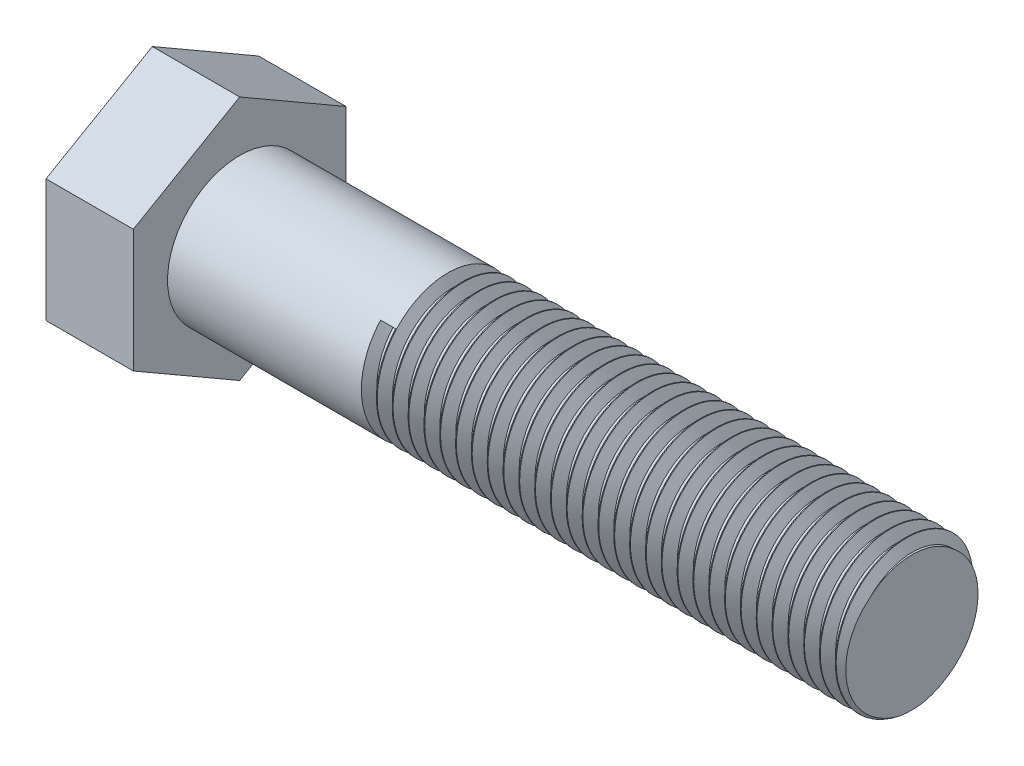
SolidWorks part; units mm, degrees
material "Chrome Stainless Steel"
ref_plane "Front Plane" through (0, 0, 0) normal (0, 0, 1) x (1, 0, 0)
ref_plane "Top Plane" through (0, 0, 0) normal (0, 1, 0) x (1, 0, 0)
ref_plane "Right Plane" through (0, 0, 0) normal (1, 0, 0) x (0, 0, -1)
sketch "Sketch1" plane through (0, 0, 0) normal (1, 0, 0) x (0, 0, -1)
  line L1 (0, -8.2122) -> (7.112, -4.1061)
  line L2 (7.112, -4.1061) -> (7.112, 4.1061)
  line L3 (7.112, 4.1061) -> (0, 8.2122)
  line L4 (0, 8.2122) -> (-7.112, 4.1061)
  line L5 (-7.112, 4.1061) -> (-7.112, -4.1061)
  line L6 (-7.112, -4.1061) -> (0, -8.2122)
  circle A0 centre (0, 0) radius 7.112 construction
  dimension "D1" = 14.224
extrude "Boss-Extrude1" add sketch "Sketch1" against normal blind 5.842
sketch "Sketch2" plane through (0, 0, 0) normal (1, 0, 0) x (0, 0, -1)
  circle A0 centre (0, 0) radius 4.826
  dimension "D1" = 9.652
extrude "Boss-Extrude2" add sketch "Sketch2" along normal blind 44.958
ref_plane "Plane1" through (44.958, 0, 0) normal (1, 0, 0) x (0, 0, -1)
sketch "Sketch6" plane through (44.958, 0, 0) normal (1, 0, 0) x (0, 0, -1)
  circle A0 centre (0, 0) radius 4.826
  dimension "D1" = 9.652
curve "Helix/Spiral1" pitch 1.0583 height 31.75 radius 4.826 centre (44.958, 0, 0) axis (-1, 0, 0) start towards (0, 0.7071, 0.7071)
sketch "Sketch7" plane through (0, 0, 0) normal (0, 0, 1) x (1, 0, 0)
  line L0 (44.958, 4.7545) -> (44.958, 5.1628) construction
  line L1 (44.958, -4.826) -> (44.958, 4.826) construction
  line L2 (44.4556, 4.826) -> (45.4604, 4.826)
  line L3 (45.4604, 4.826) -> (45.085, 4.1758)
  line L4 (45.085, 4.1758) -> (44.831, 4.1758)
  line L5 (44.958, 4.1758) -> (45.9904, 4.1758) construction
  line L7 (44.4556, 4.826) -> (44.831, 4.1758)
  spline S0 degree 3 poles (44.958, 3.4125) (44.9361, 3.8563) (44.8918, 4.576) (44.8257, 4.9513) (44.7596, 4.5748) (44.6934, 3.5013) (44.6273, 1.8949) (44.5611, 0) (44.495, -1.8949) (44.4288, -3.5013) (44.3627, -4.5747) (44.2965, -4.9516) (44.2304, -4.5747) (44.1643, -3.5013) (44.0761, -1.3594) (43.9879, 1.3594) (43.8997, 3.5013) (43.8335, 4.5747) (43.7674, 4.9516) (43.7012, 4.5747) (43.6351, 3.5013) (43.5469, 1.3594) (43.4587, -1.3594) (43.3705, -3.5013) (43.3044, -4.5747) (43.2382, -4.9516) (43.1721, -4.5747) (43.1059, -3.5013) (43.0177, -1.3594) (42.9295, 1.3594) (42.8413, 3.5013) (42.7752, 4.5747) (42.709, 4.9516) (42.6429, 4.5747) (42.5767, 3.5013) (42.4886, 1.3594) (42.4004, -1.3594) (42.3122, -3.5013) (42.246, -4.5747) (42.1799, -4.9516) (42.1137, -4.5747) (42.0476, -3.5013) (41.9594, -1.3594) (41.8712, 1.3594) (41.783, 3.5013) (41.7169, 4.5747) (41.6507, 4.9516) (41.5846, 4.5747) (41.5184, 3.5013) (41.4302, 1.3594) (41.342, -1.3594) (41.2538, -3.5013) (41.1877, -4.5747) (41.1215, -4.9516) (41.0554, -4.5747) (40.9893, -3.5013) (40.9011, -1.3594) (40.8129, 1.3594) (40.7247, 3.5013) (40.6585, 4.5747) (40.5924, 4.9516) (40.5262, 4.5747) (40.4601, 3.5013) (40.3719, 1.3594) (40.2837, -1.3594) (40.1955, -3.5013) (40.1294, -4.5747) (40.0632, -4.9516) (39.9971, -4.5747) (39.9309, -3.5013) (39.8427, -1.3594) (39.7545, 1.3594) (39.6663, 3.5013) (39.6002, 4.5747) (39.534, 4.9516) (39.4679, 4.5747) (39.4017, 3.5013) (39.3136, 1.3594) (39.2254, -1.3594) (39.1372, -3.5013) (39.071, -4.5747) (39.0049, -4.9516) (38.9387, -4.5747) (38.8726, -3.5013) (38.7844, -1.3594) (38.6962, 1.3594) (38.608, 3.5013) (38.5419, 4.5747) (38.4757, 4.9516) (38.4096, 4.5747) (38.3434, 3.5013) (38.2552, 1.3594) (38.167, -1.3594) (38.0788, -3.5013) (38.0127, -4.5747) (37.9465, -4.9516) (37.8804, -4.5747) (37.8143, -3.5013) (37.7261, -1.3594) (37.6379, 1.3594) (37.5497, 3.5013) (37.4835, 4.5747) (37.4174, 4.9516) (37.3512, 4.5747) (37.2851, 3.5013) (37.1969, 1.3594) (37.1087, -1.3594) (37.0205, -3.5013) (36.9544, -4.5747) (36.8882, -4.9516) (36.8221, -4.5747) (36.7559, -3.5013) (36.6677, -1.3594) (36.5795, 1.3594) (36.4913, 3.5013) (36.4252, 4.5747) (36.359, 4.9516) (36.2929, 4.5747) (36.2268, 3.5013) (36.1386, 1.3594) (36.0504, -1.3594) (35.9622, -3.5013) (35.896, -4.5747) (35.8299, -4.9516) (35.7637, -4.5747) (35.6976, -3.5013) (35.6094, -1.3594) (35.5212, 1.3594) (35.433, 3.5013) (35.3669, 4.5747) (35.3007, 4.9516) (35.2346, 4.5747) (35.1684, 3.5013) (35.0802, 1.3594) (34.992, -1.3594) (34.9038, -3.5013) (34.8377, -4.5747) (34.7715, -4.9516) (34.7054, -4.5747) (34.6393, -3.5013) (34.5511, -1.3594) (34.4629, 1.3594) (34.3747, 3.5013) (34.3085, 4.5747) (34.2424, 4.9516) (34.1762, 4.5747) (34.1101, 3.5013) (34.0219, 1.3594) (33.9337, -1.3594) (33.8455, -3.5013) (33.7794, -4.5747) (33.7132, -4.9516) (33.6471, -4.5747) (33.5809, -3.5013) (33.4927, -1.3594) (33.4045, 1.3594) (33.3163, 3.5013) (33.2502, 4.5747) (33.184, 4.9516) (33.1179, 4.5747) (33.0518, 3.5013) (32.9636, 1.3594) (32.8754, -1.3594) (32.7872, -3.5013) (32.721, -4.5747) (32.6549, -4.9516) (32.5887, -4.5747) (32.5226, -3.5013) (32.4344, -1.3594) (32.3462, 1.3594) (32.258, 3.5013) (32.1919, 4.5747) (32.1257, 4.9516) (32.0596, 4.5747) (31.9934, 3.5013) (31.9052, 1.3594) (31.817, -1.3594) (31.7288, -3.5013) (31.6627, -4.5747) (31.5965, -4.9516) (31.5304, -4.5747) (31.4643, -3.5013) (31.3761, -1.3594) (31.2879, 1.3594) (31.1997, 3.5013) (31.1335, 4.5747) (31.0674, 4.9516) (31.0012, 4.5747) (30.9351, 3.5013) (30.8469, 1.3594) (30.7587, -1.3594) (30.6705, -3.5013) (30.6044, -4.5747) (30.5382, -4.9516) (30.4721, -4.5747) (30.4059, -3.5013) (30.3177, -1.3594) (30.2295, 1.3594) (30.1413, 3.5013) (30.0752, 4.5747) (30.009, 4.9516) (29.9429, 4.5747) (29.8768, 3.5013) (29.7886, 1.3594) (29.7004, -1.3594) (29.6122, -3.5013) (29.546, -4.5747) (29.4799, -4.9516) (29.4137, -4.5747) (29.3476, -3.5013) (29.2594, -1.3594) (29.1712, 1.3594) (29.083, 3.5013) (29.0169, 4.5747) (28.9507, 4.9516) (28.8846, 4.5747) (28.8184, 3.5013) (28.7302, 1.3594) (28.642, -1.3594) (28.5538, -3.5013) (28.4877, -4.5747) (28.4215, -4.9516) (28.3554, -4.5747) (28.2893, -3.5013) (28.2011, -1.3594) (28.1129, 1.3594) (28.0247, 3.5013) (27.9585, 4.5747) (27.8924, 4.9516) (27.8262, 4.5747) (27.7601, 3.5013) (27.6719, 1.3594) (27.5837, -1.3594) (27.4955, -3.5013) (27.4294, -4.5747) (27.3632, -4.9516) (27.2971, -4.5747) (27.2309, -3.5013) (27.1427, -1.3594) (27.0545, 1.3594) (26.9663, 3.5013) (26.9002, 4.5747) (26.834, 4.9516) (26.7679, 4.5747) (26.7018, 3.5013) (26.6136, 1.3594) (26.5254, -1.3594) (26.4372, -3.5013) (26.371, -4.5747) (26.3049, -4.9516) (26.2387, -4.5747) (26.1726, -3.5013) (26.0844, -1.3594) (25.9962, 1.3594) (25.908, 3.5013) (25.8419, 4.5747) (25.7757, 4.9516) (25.7096, 4.5747) (25.6434, 3.5013) (25.5552, 1.3594) (25.467, -1.3594) (25.3788, -3.5013) (25.3127, -4.5747) (25.2465, -4.9516) (25.1804, -4.5747) (25.1143, -3.5013) (25.0261, -1.3594) (24.9379, 1.3594) (24.8497, 3.5013) (24.7835, 4.5747) (24.7174, 4.9516) (24.6512, 4.5747) (24.5851, 3.5013) (24.4969, 1.3594) (24.4087, -1.3594) (24.3205, -3.5013) (24.2544, -4.5747) (24.1882, -4.9516) (24.1221, -4.5747) (24.0559, -3.5013) (23.9677, -1.3594) (23.8795, 1.3594) (23.7913, 3.5013) (23.7252, 4.5747) (23.659, 4.9516) (23.5929, 4.5747) (23.5268, 3.5013) (23.4386, 1.3594) (23.3504, -1.3594) (23.2622, -3.5013) (23.196, -4.5747) (23.1299, -4.9516) (23.0637, -4.5747) (22.9976, -3.5013) (22.9094, -1.3594) (22.8212, 1.3594) (22.733, 3.5013) (22.6669, 4.5747) (22.6007, 4.9516) (22.5346, 4.5747) (22.4684, 3.5013) (22.3802, 1.3594) (22.292, -1.3594) (22.2038, -3.5013) (22.1377, -4.5747) (22.0715, -4.9516) (22.0054, -4.5747) (21.9393, -3.5013) (21.8511, -1.3594) (21.7629, 1.3594) (21.6747, 3.5013) (21.6085, 4.5747) (21.5424, 4.9516) (21.4762, 4.5747) (21.4101, 3.5013) (21.3219, 1.3594) (21.2337, -1.3594) (21.1455, -3.5013) (21.0794, -4.5747) (21.0132, -4.9516) (20.9471, -4.5747) (20.8809, -3.5013) (20.7927, -1.3594) (20.7045, 1.3594) (20.6163, 3.5013) (20.5502, 4.5747) (20.484, 4.9516) (20.4179, 4.5747) (20.3518, 3.5013) (20.2636, 1.3594) (20.1754, -1.3594) (20.0872, -3.5013) (20.021, -4.5747) (19.9549, -4.9516) (19.8887, -4.5747) (19.8226, -3.5013) (19.7344, -1.3594) (19.6462, 1.3594) (19.558, 3.5013) (19.4919, 4.5747) (19.4257, 4.9516) (19.3596, 4.5747) (19.2934, 3.5013) (19.2052, 1.3594) (19.117, -1.3594) (19.0288, -3.5013) (18.9627, -4.5747) (18.8965, -4.9516) (18.8304, -4.5747) (18.7643, -3.5013) (18.6761, -1.3594) (18.5879, 1.3594) (18.4997, 3.5013) (18.4335, 4.5747) (18.3674, 4.9516) (18.3012, 4.5747) (18.2351, 3.5013) (18.1469, 1.3594) (18.0587, -1.3594) (17.9705, -3.5013) (17.9044, -4.5747) (17.8382, -4.9516) (17.7721, -4.5747) (17.7059, -3.5013) (17.6177, -1.3594) (17.5295, 1.3594) (17.4413, 3.5013) (17.3752, 4.5747) (17.309, 4.9516) (17.2429, 4.5747) (17.1768, 3.5013) (17.0886, 1.3594) (17.0004, -1.3594) (16.9122, -3.5013) (16.846, -4.5747) (16.7799, -4.9516) (16.7137, -4.5747) (16.6476, -3.5013) (16.5594, -1.3594) (16.4712, 1.3594) (16.383, 3.5013) (16.3169, 4.5747) (16.2507, 4.9516) (16.1846, 4.5747) (16.1184, 3.5013) (16.0302, 1.3594) (15.942, -1.3594) (15.8538, -3.5013) (15.7877, -4.5747) (15.7215, -4.9516) (15.6554, -4.5747) (15.5893, -3.5013) (15.5011, -1.3594) (15.4129, 1.3594) (15.3247, 3.5013) (15.2585, 4.5747) (15.1924, 4.9516) (15.1262, 4.5747) (15.0601, 3.5013) (14.9719, 1.3594) (14.8837, -1.3594) (14.7955, -3.5013) (14.7294, -4.5747) (14.6632, -4.9516) (14.5971, -4.5747) (14.5309, -3.5013) (14.4427, -1.3594) (14.3545, 1.3594) (14.2663, 3.5013) (14.2002, 4.5747) (14.134, 4.9516) (14.0679, 4.5747) (14.0017, 3.5013) (13.9136, 1.3594) (13.8254, -1.3594) (13.7372, -3.5013) (13.671, -4.5747) (13.6049, -4.9516) (13.5387, -4.5747) (13.4726, -3.5013) (13.4064, -1.895) (13.3403, 0.0003) (13.2742, 1.8936) (13.2299, 2.9687) (13.208, 3.4125) knots 0 0 0 0 0.002083 0.004167 0.00625 0.008333 0.010417 0.0125 0.014583 0.016667 0.01875 0.020833 0.022917 0.025 0.027083 0.03125 0.033333 0.035417 0.0375 0.039583 0.041667 0.04375 0.047917 0.05 0.052083 0.054167 0.05625 0.058333 0.060417 0.064583 0.066667 0.06875 0.070833 0.072917 0.075 0.077083 0.08125 0.083333 0.085417 0.0875 0.089583 0.091667 0.09375 0.097917 0.1 0.102083 0.104167 0.10625 0.108333 0.110417 0.114583 0.116667 0.11875 0.120833 0.122917 0.125 0.127083 0.13125 0.133333 0.135417 0.1375 0.139583 0.141667 0.14375 0.147917 0.15 0.152083 0.154167 0.15625 0.158333 0.160417 0.164583 0.166667 0.16875 0.170833 0.172917 0.175 0.177083 0.18125 0.183333 0.185417 0.1875 0.189583 0.191667 0.19375 0.197917 0.2 0.202083 0.204167 0.20625 0.208333 0.210417 0.214583 0.216667 0.21875 0.220833 0.222917 0.225 0.227083 0.23125 0.233333 0.235417 0.2375 0.239583 0.241667 0.24375 0.247917 0.25 0.252083 0.254167 0.25625 0.258333 0.260417 0.264583 0.266667 0.26875 0.270833 0.272917 0.275 0.277083 0.28125 0.283333 0.285417 0.2875 0.289583 0.291667 0.29375 0.297917 0.3 0.302083 0.304167 0.30625 0.308333 0.310417 0.314583 0.316667 0.31875 0.320833 0.322917 0.325 0.327083 0.33125 0.333333 0.335417 0.3375 0.339583 0.341667 0.34375 0.347917 0.35 0.352083 0.354167 0.35625 0.358333 0.360417 0.364583 0.366667 0.36875 0.370833 0.372917 0.375 0.377083 0.38125 0.383333 0.385417 0.3875 0.389583 0.391667 0.39375 0.397917 0.4 0.402083 0.404167 0.40625 0.408333 0.410417 0.414583 0.416667 0.41875 0.420833 0.422917 0.425 0.427083 0.43125 0.433333 0.435417 0.4375 0.439583 0.441667 0.44375 0.447917 0.45 0.452083 0.454167 0.45625 0.458333 0.460417 0.464583 0.466667 0.46875 0.470833 0.472917 0.475 0.477083 0.48125 0.483333 0.485417 0.4875 0.489583 0.491667 0.49375 0.497917 0.5 0.502083 0.504167 0.50625 0.508333 0.510417 0.514583 0.516667 0.51875 0.520833 0.522917 0.525 0.527083 0.53125 0.533333 0.535417 0.5375 0.539583 0.541667 0.54375 0.547917 0.55 0.552083 0.554167 0.55625 0.558333 0.560417 0.564583 0.566667 0.56875 0.570833 0.572917 0.575 0.577083 0.58125 0.583333 0.585417 0.5875 0.589583 0.591667 0.59375 0.597917 0.6 0.602083 0.604167 0.60625 0.608333 0.610417 0.614583 0.616667 0.61875 0.620833 0.622917 0.625 0.627083 0.63125 0.633333 0.635417 0.6375 0.639583 0.641667 0.64375 0.647917 0.65 0.652083 0.654167 0.65625 0.658333 0.660417 0.664583 0.666667 0.66875 0.670833 0.672917 0.675 0.677083 0.68125 0.683333 0.685417 0.6875 0.689583 0.691667 0.69375 0.697917 0.7 0.702083 0.704167 0.70625 0.708333 0.710417 0.714583 0.716667 0.71875 0.720833 0.722917 0.725 0.727083 0.73125 0.733333 0.735417 0.7375 0.739583 0.741667 0.74375 0.747917 0.75 0.752083 0.754167 0.75625 0.758333 0.760417 0.764583 0.766667 0.76875 0.770833 0.772917 0.775 0.777083 0.78125 0.783333 0.785417 0.7875 0.789583 0.791667 0.79375 0.797917 0.8 0.802083 0.804167 0.80625 0.808333 0.810417 0.814583 0.816667 0.81875 0.820833 0.822917 0.825 0.827083 0.83125 0.833333 0.835417 0.8375 0.839583 0.841667 0.84375 0.847917 0.85 0.852083 0.854167 0.85625 0.858333 0.860417 0.864583 0.866667 0.86875 0.870833 0.872917 0.875 0.877083 0.88125 0.883333 0.885417 0.8875 0.889583 0.891667 0.89375 0.897917 0.9 0.902083 0.904167 0.90625 0.908333 0.910417 0.914583 0.916667 0.91875 0.920833 0.922917 0.925 0.927083 0.93125 0.933333 0.935417 0.9375 0.939583 0.941667 0.94375 0.947917 0.95 0.952083 0.954167 0.95625 0.958333 0.960417 0.964583 0.966667 0.96875 0.970833 0.972917 0.975 0.977083 0.98125 0.983333 0.985417 0.9875 0.989583 0.991667 0.99375 0.995833 0.997917 1 1 1 1 construction
  point P13 (44.958, 4.826)
  dimension "D1" = 0.127
  dimension "D2" = 0.6502
  dimension "D3" = 60
sweep "Cut-Sweep1" cut profiles "Sketch7" path "Helix/Spiral1" align with end faces yes
